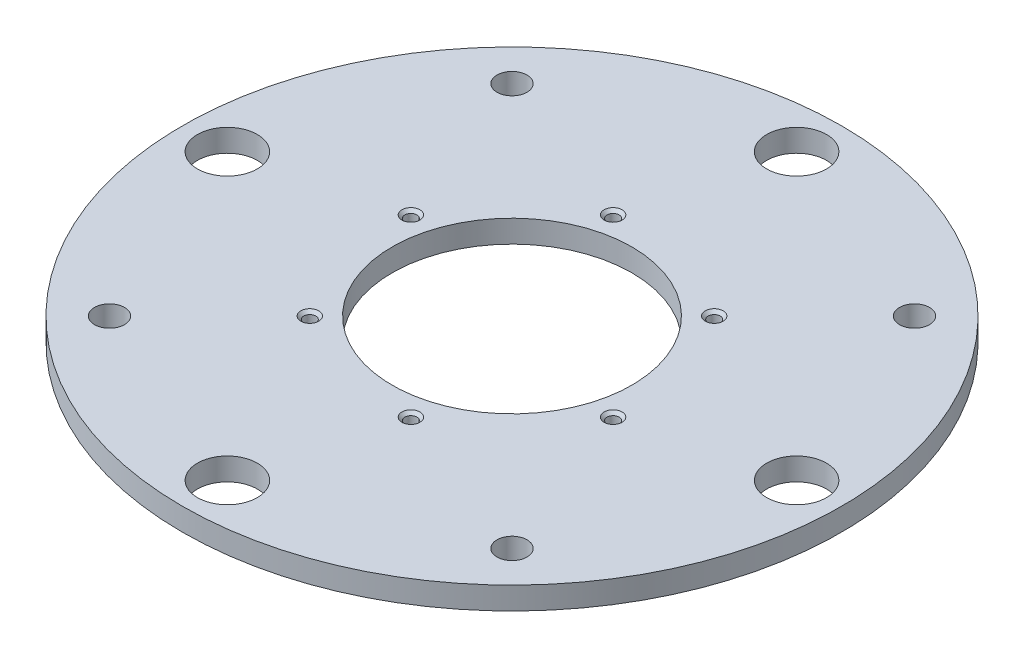
SolidWorks part; units mm, degrees
material "6061-T4 (SS)"
ref_plane "Front Plane" through (0, 0, 0) normal (0, 0, 1) x (1, 0, 0)
ref_plane "Top Plane" through (0, 0, 0) normal (0, 1, 0) x (1, 0, 0)
ref_plane "Right Plane" through (0, 0, 0) normal (1, 0, 0) x (0, 0, -1)
sketch "Sketch2" plane through (0, 0, 0) normal (0, 1, 0) x (1, 0, 0)
  circle A0 centre (0, 0) radius 50.8
  circle A1 centre (0, 0) radius 139.7
  dimension "D1" = 101.6
  dimension "D2" = 279.4
extrude "Boss-Extrude1" add sketch "Sketch2" along normal blind 9.525
sketch "Sketch3" plane through (0, 9.525, 0) normal (0, 1, 0) x (1, 0, 0)
  line L0 (0, 0) -> (0, 120.65) construction
  line L1 (0, 0) -> (42.8583, 42.8583) construction
  line L2 (42.8583, 42.8583) -> (103.2729, 103.2729) construction
  circle A0 centre (42.8583, 42.8583) radius 3.175
  circle A1 centre (0, 0) radius 120.65 construction
  circle A2 centre (0, 120.65) radius 12.6746
  circle A3 centre (120.65, 0) radius 12.6746
  circle A4 centre (0, -120.65) radius 12.6746
  circle A5 centre (-120.65, 0) radius 12.6746
  circle A6 centre (0, 0) radius 60.6107 construction
  circle A8 centre (58.5455, -15.6872) radius 3.175
  circle A9 centre (15.6872, -58.5455) radius 3.175
  circle A10 centre (0, 0) radius 139.7 construction
  circle A11 centre (-42.8583, -42.8583) radius 3.175
  circle A12 centre (-58.5455, 15.6872) radius 3.175
  circle A13 centre (-15.6872, 58.5455) radius 3.175
  circle A14 centre (85.3124, 85.3124) radius 6.35
  circle A15 centre (85.3124, -85.3124) radius 6.35
  circle A16 centre (-85.3124, -85.3124) radius 6.35
  circle A17 centre (-85.3124, 85.3124) radius 6.35
  point P17 (0, 0)
  point P26 (0, 0)
  point P33 (0, 0)
  point P39 (0, 0)
  point P43 (0, 0)
  dimension "D1" = 241.3
  dimension "D2" = 25.3492
  dimension "D5" = 60.6107
  dimension "D7" = 6.35
  dimension "D9" = 12.7
  dimension "D10" = 45
  dimension "D4" = 45
  dimension "D3" = 4
  dimension "D8" = 6
  dimension "D11" = 4
extrude "Cut-Extrude2" cut sketch "Sketch3" against normal through all contours A5 | A17 | A2 | A14 | A3 | A15 | A4 | A16
sketch "Sketch4" plane through (0, 9.525, 0) normal (0, 1, 0) x (1, 0, 0)
  circle A1 centre (0, 0) radius 139.7
  circle A2 centre (0, 0) radius 139.7
  circle A3 centre (85.3124, 85.3124) radius 6.35
  circle A4 centre (85.3124, 85.3124) radius 6.35
  circle A5 centre (0, -120.65) radius 12.6746
  circle A6 centre (0, -120.65) radius 12.6746
  circle A7 centre (120.65, 0) radius 12.6746
  circle A8 centre (120.65, 0) radius 12.6746
  circle A9 centre (0, 120.65) radius 12.6746
  circle A10 centre (0, 120.65) radius 12.6746
  circle A11 centre (42.8583, 42.8583) radius 3.175
  circle A12 centre (42.8583, 42.8583) radius 3.175
  circle A13 centre (-15.6872, 58.5455) radius 3.175
  circle A14 centre (-15.6872, 58.5455) radius 3.175
  circle A15 centre (-58.5455, 15.6872) radius 3.175
  circle A16 centre (-58.5455, 15.6872) radius 3.175
  circle A17 centre (-42.8583, -42.8583) radius 3.175
  circle A18 centre (-42.8583, -42.8583) radius 3.175
  circle A19 centre (15.6872, -58.5455) radius 3.175
  circle A20 centre (15.6872, -58.5455) radius 3.175
  circle A21 centre (58.5455, -15.6872) radius 3.175
  circle A22 centre (58.5455, -15.6872) radius 3.175
  circle A23 centre (-120.65, 0) radius 12.6746
  circle A24 centre (-120.65, 0) radius 12.6746
  circle A25 centre (-85.3124, 85.3124) radius 6.35
  circle A26 centre (-85.3124, 85.3124) radius 6.35
  circle A27 centre (-85.3124, -85.3124) radius 6.35
  circle A28 centre (-85.3124, -85.3124) radius 6.35
  circle A29 centre (85.3124, -85.3124) radius 6.35
  circle A30 centre (85.3124, -85.3124) radius 6.35
  dimension "D1" = 0
  dimension "D2" = 0
  dimension "D3" = 0
  dimension "D4" = 0
  dimension "D5" = 0
  dimension "D6" = 0
  dimension "D7" = 0
  dimension "D8" = 0
  dimension "D9" = 0
  dimension "D10" = 0
  dimension "D11" = 0
  dimension "D12" = 0
  dimension "D13" = 0
  dimension "D14" = 0
  dimension "D15" = 0
hole_wizard "1/4-20 Tapped Hole1" positions "Sketch5" profile "Sketch6" tap size "1/4-20" standard "ANSI Inch" end condition through all
sketch "Sketch5" plane through (0, 9.525, 0) normal (0, 1, 0) x (1, 0, 0)
  point P0 (-58.5455, 15.6872)
  point P3 (-15.6872, 58.5455)
  point P6 (42.8583, 42.8583)
  point P9 (58.5455, -15.6872)
  point P12 (15.6872, -58.5455)
  point P15 (-42.8583, -42.8583)
sketch "Sketch6" plane through (-58.5455, 9.525, -15.6872) normal (1, 0, 0) x (0, 0, 1)
  line L0 (0, 0) -> (0, 9.525)
  line L1 (0, 9.525) -> (3.81, 9.525)
  line L2 (2.5527, 8.2677) -> (2.5527, 1.2573)
  line L3 (2.5527, 1.2573) -> (3.81, 0)
  line L5 (3.81, 0) -> (0, 0)
  line L6 (-2.5527, 1.2573) -> (-3.81, 0) construction
  line L7 (3.81, 9.525) -> (2.5527, 8.2677)
  line L8 (-3.81, 9.525) -> (-2.5527, 8.2677) construction
  line L11 (0, -6.35) -> (0, 107.95) construction
  dimension "Thru Tap Drill Dia." = 5.1054
  dimension "Thru Tap Drill Depth" = 9.525
  dimension "Near C'Sink Dia." = 7.62
  dimension "Near C'Sink Angle" = 90
  dimension "Far C'Sink Dia." = 7.62
  dimension "Far C'Sink Angle" = 90
cosmetic thread "Hole Thread1" parameters "D2"=6.35
cosmetic thread "Hole Thread2" parameters "D2"=6.35
cosmetic thread "Hole Thread3" parameters "D2"=6.35
cosmetic thread "Hole Thread4" parameters "D2"=6.35
cosmetic thread "Hole Thread5" parameters "D2"=6.35
cosmetic thread "Hole Thread6" parameters "D2"=6.35
sketch "Sketch7" plane through (0, 9.525, 0) normal (0, 1, 0) x (1, 0, 0)
  line L1 (-152.4, -152.4) -> (152.4, -152.4) construction
  line L2 (-152.4, -152.4) -> (-152.4, 152.4) construction
  line L3 (-152.4, 152.4) -> (152.4, 152.4) construction
  line L4 (152.4, -152.4) -> (152.4, 152.4) construction
  line L5 (-152.4, -152.4) -> (152.4, 152.4) construction
  line L6 (-152.4, 152.4) -> (152.4, -152.4) construction
  point P0 (0, 0)
  dimension "D1" = 304.8
